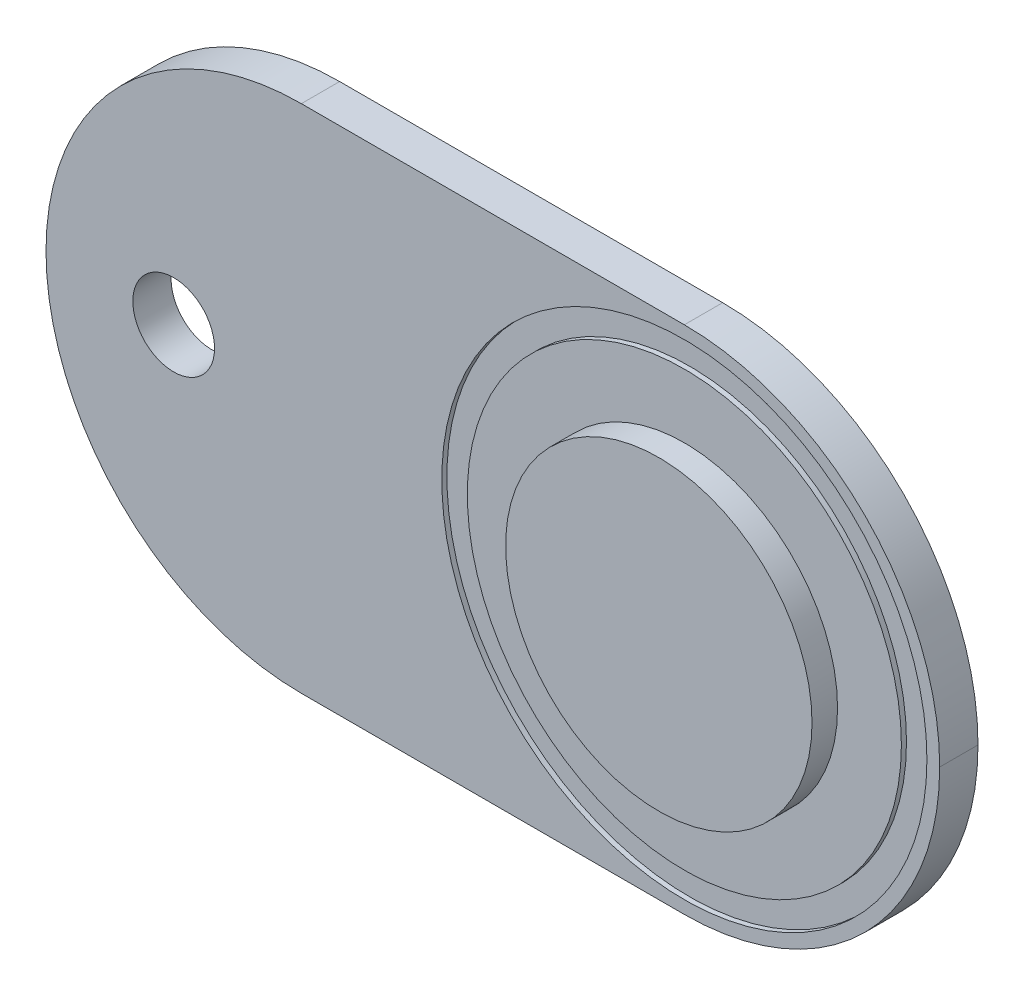
SolidWorks part; units mm, degrees
ref_plane "Front" through (0, 0, 0) normal (0, 0, 1) x (1, 0, 0)
ref_plane "Top" through (0, 0, 0) normal (0, 1, 0) x (1, 0, 0)
ref_plane "Right" through (0, 0, 0) normal (1, 0, 0) x (0, 0, -1)
sketch "Sketch1" plane through (0, 0, 0) normal (0, 0, 1) x (1, 0, 0)
  line L1 (0, 10) -> (35, 10)
  line L2 (0, 10) -> (0, -10)
  line L3 (0, -10) -> (35, -10)
  line L4 (35, 10) -> (35, -10)
  dimension "D1" = 20
  dimension "D2" = 35
extrude "Boss-Extrude1" add sketch "Sketch1" along normal blind 1.5
sketch "Sketch2" plane through (0, 0, 1.5) normal (0, 0, 1) x (1, 0, 0)
  circle A0 centre (5, 0) radius 1.6
  dimension "D1" = 3.2
  dimension "D2" = 5
extrude "Cut-M3 Hole" cut sketch "Sketch2" against normal through all
sketch "Sketch3" plane through (0, 0, 1.5) normal (0, 0, 1) x (1, 0, 0)
  circle A0 centre (25, 0) radius 6
  circle A1 centre (5, 0) radius 1.6 construction
  dimension "D1" = 12
  dimension "D2" = 20
extrude "Boss-FSR Boss" add sketch "Sketch3" along normal blind 1
fillet "Fillet1" radius 10 4 edges at (0, 10, 0.75) (35, 10, 0.75) (35, -10, 0.75) (0, -10, 0.75)
sketch "Sketch4" plane through (0, 0, 1.5) normal (0, 0, 1) x (1, 0, 0)
  circle A0 centre (25, 0) radius 9.5
  arc A1 (25, -10) -> (35, 0) centre (25, 0) ccw construction
  dimension "D1" = 19
extrude "Cut-Extrude-Thin1" cut sketch "Sketch4" against normal blind 0.2 thin thin type one direction reverse wall 1
